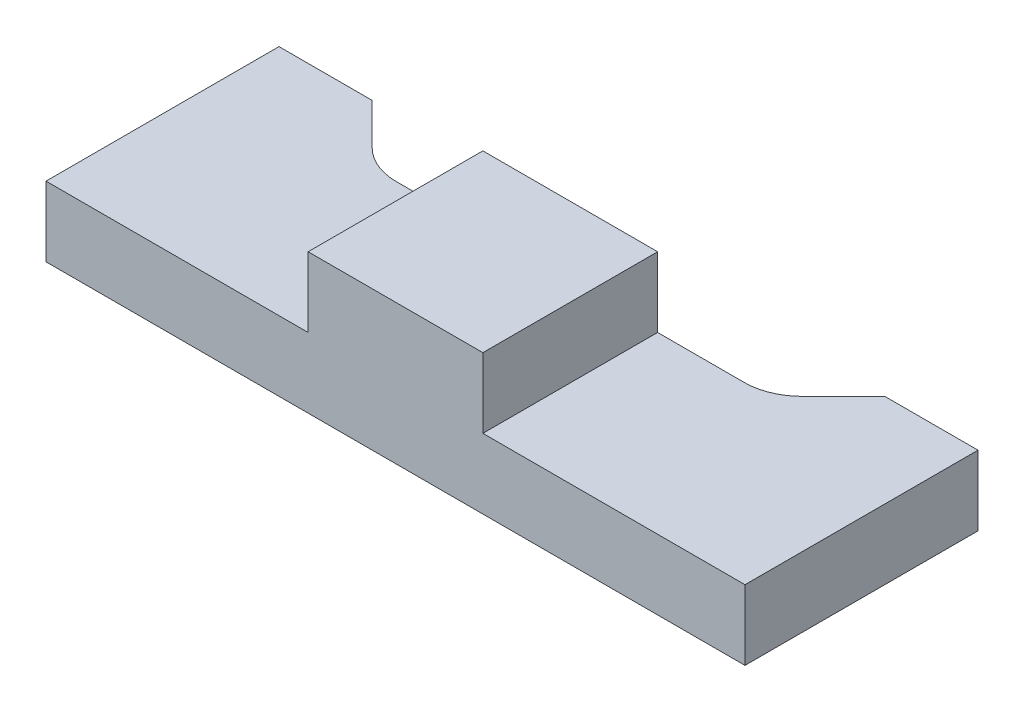
SolidWorks part; units mm, degrees
material "1060 Alloy"
ref_plane "Front Plane" through (0, 0, 0) normal (0, 0, 1) x (1, 0, 0)
ref_plane "Top Plane" through (0, 0, 0) normal (0, 1, 0) x (1, 0, 0)
ref_plane "Right Plane" through (0, 0, 0) normal (1, 0, 0) x (0, 0, -1)
sketch "Sketch4" plane through (0, 0, 0) normal (0, 0, 1) x (1, 0, 0)
  line L0 (-30, 0) -> (30, 0)
  line L1 (30, 0) -> (30, 6)
  line L2 (30, 6) -> (7.5, 6)
  line L3 (7.5, 6) -> (7.5, 12)
  line L4 (7.5, 12) -> (-7.5, 12)
  line L5 (-7.5, 12) -> (-7.5, 6)
  line L6 (-7.5, 6) -> (-30, 6)
  line L7 (-30, 6) -> (-30, 0)
  dimension "D1" = 6
  dimension "D2" = 60
  dimension "D3" = 15
  dimension "D4" = 12
extrude "Boss-Extrude2" add sketch "Sketch4" along normal blind 20
hole_wizard "Tap Drill for M6 Tap2" positions "Sketch6" profile "Sketch5" hole size "M6" standard "ISO"
sketch "Sketch6" plane through (0, 0, 0) normal (0, 0, -1) x (-1, 0, 0)
  line L0 (-7.5, 12) -> (7.5, 12) construction
  point P0 (0, 6)
  dimension "D1" = 6
sketch "Sketch5" plane through (0, 6, 0) normal (1, 0, 0) x (0, 1, 0)
  line L0 (0, 0) -> (0, 9.5022)
  line L1 (0, 9.5022) -> (2.5, 8)
  line L2 (2.5, 8) -> (2.5, 0)
  line L5 (2.5, 0) -> (0, 0)
  line L10 (0, 9.5022) -> (-2.5, 8) construction
  line L11 (0, -6.35) -> (0, 107.95) construction
  dimension "Hole Dia." = 5
  dimension "Hole Depth" = 8
  dimension "Drill Angle" = 118
sketch "Sketch7" plane through (0, 12, 0) normal (0, 1, 0) x (1, 0, 0)
  line L0 (-7.5, 0) -> (-30, 0) construction
  line L1 (-22, 0) -> (22, 0)
  line L2 (-22, 0) -> (-17, -5)
  line L3 (-17, -5) -> (17, -5)
  line L4 (22, 0) -> (17, -5)
  line L5 (30, 0) -> (7.5, 0) construction
  dimension "D1" = 45
  dimension "D2" = 45
  dimension "D3" = 34
  dimension "D4" = 17
  dimension "D5" = 5
extrude "Cut-Extrude1" cut sketch "Sketch7" against normal up to next
fillet "Fillet1" radius 5 2 edges at (-17, 3, 5) (17, 3, 5)
